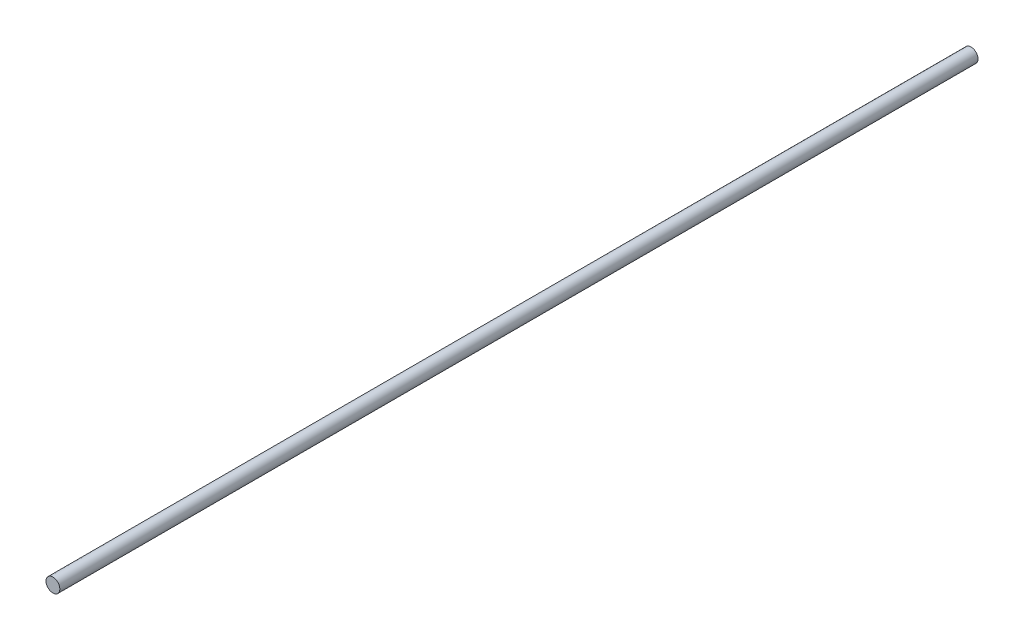
SolidWorks part; units mm, degrees
material "Alliage de zinc AC41A, brut"
ref_plane "Front Plane" through (0, 0, 0) normal (0, 0, 1) x (1, 0, 0)
ref_plane "Top Plane" through (0, 0, 0) normal (0, 1, 0) x (1, 0, 0)
ref_plane "Right Plane" through (0, 0, 0) normal (1, 0, 0) x (0, 0, -1)
sketch "Sketch1" plane through (0, 0, 0) normal (0, 0, 1) x (1, 0, 0)
  circle A0 centre (0, 0) radius 6.35
  dimension "D1" = 12.7
extrude "Boss-Extrude1" add sketch "Sketch1" along normal blind 914.4
sketch "Sketch2" [suppressed] plane through (0, 0, 0) normal (0, 1, 0) x (1, 0, 0)
  line L0 (6.35, -914.4) -> (6.35, 0) construction
  line L1 (-6.35, -914.4) -> (6.35, -914.4)
  line L2 (-6.35, -914.4) -> (-6.35, -762)
  line L3 (-6.35, -762) -> (6.35, -762)
  line L4 (6.35, -914.4) -> (6.35, -762)
  dimension "D1" = 152.4
extrude "Cut-Extrude1" [suppressed] cut sketch "Sketch2" against normal blind 25.4 and the other way blind 25.4
sketch "Esquisse1" plane through (0, 0, 914.4) normal (0, 0, 1) x (1, 0, 0)
  circle A0 centre (0, 0) radius 6.35
extrude "Enlèv. mat.-Extru.1" cut sketch "Esquisse1" against normal blind 34.29
sketch "Esquisse2" [suppressed] plane through (0, 0, 762) normal (0, 0, 1) x (1, 0, 0)
  circle A0 centre (0, 0) radius 6.35
  dimension "D1" = 12.7
extrude "Enlèv. mat.-Extru.2" [suppressed] cut sketch "Esquisse2" against normal blind 504.19
sketch "Esquisse3" plane through (0, 0, 0) normal (0, 1, 0) x (1, 0, 0)
  line L0 (6.35, -880.11) -> (6.35, 0) construction
  line L1 (-6.35, 0) -> (6.35, 0)
  line L2 (-6.35, 0) -> (-6.35, -38.1)
  line L3 (-6.35, -38.1) -> (6.35, -38.1)
  line L4 (6.35, 0) -> (6.35, -38.1)
  dimension "D1" = 38.1
extrude "Enlèv. mat.-Extru.3" cut sketch "Esquisse3" against normal through all and the other way through all
